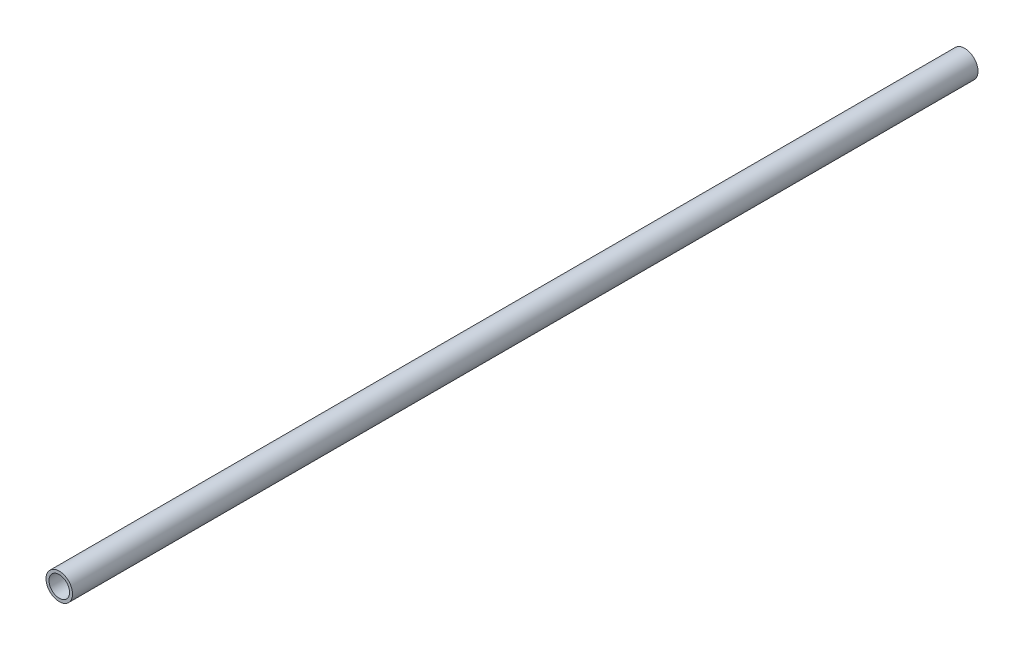
SolidWorks part; units mm, degrees
ref_plane "Front Plane" through (0, 0, 0) normal (0, 0, 1) x (1, 0, 0)
ref_plane "Top Plane" through (0, 0, 0) normal (0, 1, 0) x (1, 0, 0)
ref_plane "Right Plane" through (0, 0, 0) normal (1, 0, 0) x (0, 0, -1)
sketch "Sketch3" plane through (0, 0, 40.7745) normal (0, 0, -1) x (-1, 0, 0)
  circle A0 centre (0, 0) radius 7.9375
  arc A2 (-2.3597, -7.5786) -> (2.3597, 7.5786) centre (0, 0) ccw construction
  arc A4 (1.8273, 5.8689) -> (-1.8273, -5.8689) centre (0, 0) ccw construction
  arc A5 (-1.8273, -5.8689) -> (1.8273, 5.8689) centre (0, 0) ccw construction
  arc A6 (1.8273, 5.8689) -> (-1.8273, -5.8689) centre (0, 0) ccw
  arc A7 (-1.8273, -5.8689) -> (1.8273, 5.8689) centre (0, 0) ccw
extrude "Boss-Extrude2" add sketch "Sketch3" along normal up to surface (542.0274 mm away)
